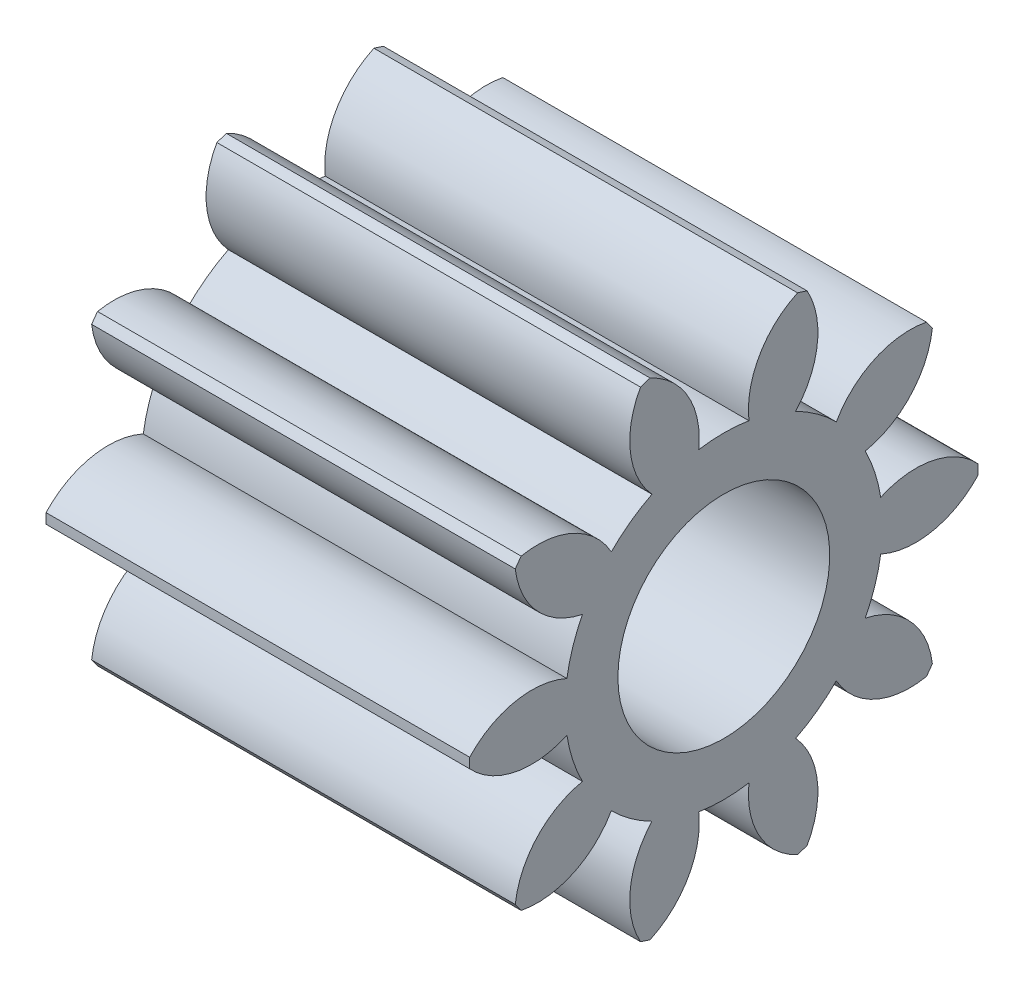
SolidWorks part; units mm, degrees
ref_plane "Plane1" through (0, 0, 0) normal (0, 0, 1) x (1, 0, 0)
ref_plane "Plane2" through (0, 0, 0) normal (0, 1, 0) x (1, 0, 0)
ref_plane "Plane3" through (0, 0, 0) normal (1, 0, 0) x (0, 0, -1)
other "Configuration Table"
sketch "HoldingSke" plane through (0, 0, 0) normal (0, 1, 0) x (1, 0, 0)
  line L0 (0, 0) -> (0.9848, -0.1736)
  line L1 (-15, 0) -> (100, 0) construction
  line L2 (0, 0) -> (-2.1039, 2.3779)
  line L3 (0, 0) -> (-11.863, 4.5341)
  line L4 (0, 0) -> (8.5048, 1.4996)
  line L5 (0, 0) -> (-46.8476, -17.4728)
  line L6 (0, 0) -> (-8.2896, -5.593)
  line L7 (-2.1039, 2.3779) -> (8.6586, 51.2059)
  line L8 (-76.2, 54.61) -> (-75.3, 54.61)
  line L9 (-71.009, 38.7566) -> (-53.1078, 45.2721)
  line L10 (-76.2, 71.12) -> (104.1128, 71.12)
  line L11 (0, 0) -> (-10, 0)
  line L12 (-76.2, 101.6) -> (-76.162, 101.6)
  line L13 (24.9733, 27.94) -> (52.9518, 28.4284)
  line L14 (24.9733, 27.94) -> (24.9743, 27.94)
  line L15 (24.9733, 27.94) -> (100.4006, 29.5858)
  line L16 (-63.627, -1) -> (-12.827, -1)
  circle A0 centre (0, 0) radius 2.5
  circle A1 centre (0, 0) radius 3.749
  circle A2 centre (0, 0) radius 37.5
  circle A3 centre (0, 0) radius 2.5
  dimension "Num_teeth" = 10
  dimension "Pitch_radius" = 180.3128
  dimension "Width" = 10
  dimension "Thickness" = 10
sketch "BasProSke" plane through (0, 0, 0) normal (0, 1, 0) x (1, 0, 0)
  line L0 (-10, 0) -> (60, 0) construction
  line L1 (0, 0) -> (0, 6)
  line L2 (0, 0) -> (10, 0)
  line L3 (10, 0) -> (10, 6)
  line L4 (10, 6) -> (0, 6)
  dimension "Thickness" = 10
  dimension "Diameter" = 12
revolve "Base-Revolve" add sketch "BasProSke" angle 360 about L0
sketch "TooCutSke" plane through (0, 0, 0) normal (1, 0, 0) x (0, 0, -1)
  line L1 (0, 0) -> (0, 107) construction
  line L2 (0, 0) -> (-0.8485, 4.9275) construction
  line L3 (0, 0) -> (-3.0584, 9.4126) construction
  line L4 (-0.8485, 4.9275) -> (-1.5292, 4.7063) construction
  arc A0 (0.5928, 3.7018) -> (-0.5928, 3.7018) centre (0, 0) ccw
  arc A1 (1.7758, 5.7578) -> (-1.7758, 5.7578) centre (0, 0) ccw
  circle A2 centre (0, 0) radius 5 construction
  circle A3 centre (0, 0) radius 4.6985 construction
  arc A4 (-0.5928, 3.7018) -> (-1.7758, 5.7578) centre (-2.5801, 3.9267) ccw
  arc A5 (1.7758, 5.7578) -> (0.5928, 3.7018) centre (2.5801, 3.9267) ccw
extrude "ToothCut" cut sketch "TooCutSke" along normal through all
fillet "Breaks" [suppressed] radius 0.02 tangent propagation no
fillet "RootFillets" [suppressed] radius 0.251
pattern_circular "TeethCuts" count 10 every 36 about axis through (-10, 0, 0) along (1, 0, 0) of "ToothCut", "RootFillets", "Breaks"
sketch "HubNeaOneSke" plane through (0, 0, 0) normal (-1, 0, 0) x (0, 0, 1)
  circle A0 centre (0, 0) radius 3.749
  dimension "Diameter" = 7.498
extrude "HubNearOne" [suppressed] add sketch "HubNeaOneSke" along normal blind 40.0001
sketch "HubNeaBotSke" plane through (0, 0, 0) normal (-1, 0, 0) x (0, 0, 1)
  circle A0 centre (0, 0) radius 3.749
  dimension "Diameter" = 7.498
extrude "HubNearBoth" [suppressed] add sketch "HubNeaBotSke" along normal blind 20
ref_plane "FarPln" through (10, 0, 0) normal (1, 0, 0) x (0, 0, -1)
sketch "HubFarSke" plane through (10, 0, 0) normal (1, 0, 0) x (0, 0, -1)
  circle A0 centre (0, 0) radius 3.749
  dimension "Diameter" = 7.498
extrude "HubFar" [suppressed] add sketch "HubFarSke" along normal blind 20
sketch "BorSke" plane through (0, 0, 0) normal (1, 0, 0) x (0, 0, -1)
  circle A0 centre (0, 0) radius 2.5
  dimension "Diameter" = 5
extrude "Bore" cut sketch "BorSke" along normal mid plane 100.0001
sketch "KeySke" plane through (0, 0, 0) normal (1, 0, 0) x (0, 0, -1)
  line L0 (-1, 0) -> (-1, 3.4)
  line L1 (-1, 3.4) -> (1, 3.4)
  line L2 (1, 3.4) -> (1, 0)
  line L3 (0, 0) -> (0, 34) construction
  line L4 (-1, 0) -> (1, 0)
  dimension "Width" = 2
extrude "Keyway" [suppressed] cut sketch "KeySke" along normal mid plane 100.0001
pattern_circular "Keyway2" [suppressed] count 2 every 90 about axis through (-10, 0, 0) along (1, 0, 0) reverse direction yes
equation "' \"Module@HoldingSke\" = 6.35"
equation "' \"Num_teeth@HoldingSke\" = 12"
equation "' \"Ap@HoldingSke\" =  20"
equation "' \"Ap@HoldingSke\" = 20"
equation "' \"Width@HoldingSke\" = 0.5 * 25.4"
equation "' \"Hub_dia@HoldingSke\"= 1 * 25.4"
equation "' \"Hub_dia@HoldingSke\" = 1 * 25.4"
equation "' \"Overall_len@HoldingSke\" = 1.0 * 25.4"
equation "' \"Bore@HoldingSke\" = 0.75 * 25.4"
equation "' \"T_dim@HoldingSke\" = 0.1 * 25.4"
equation "' \"Width@KeySke\" = 0.25 * 25.4"
equation "' \"Show_teeth@HoldingSke\" = 13"
equation "' \"Backlash@HoldingSke\" = 0.009 * 25.4"
equation "' \"Addendum_fac@HoldingSke\" = 1.0"
equation "' \"Dedendum_fac@HoldingSke\" = 1.25"
equation "' \"Dedendum_add@HoldingSke\" = 0.00005 * 25.4"
equation "' \"Clearance_fac@HoldingSke\" = 0.25"
equation "\"Pitch@HoldingSke\" = 1 / \"Module@HoldingSke\""
equation "\"Overcut_dia@TooCutSke\" = (\"Num_teeth@HoldingSke\" + 2 * \"Addendum_fac@HoldingSke\") / \"Pitch@HoldingSke\" + 0.002 * 25.4"
equation "\"Pitch_dia@TooCutSke\" = \"Num_teeth@HoldingSke\" / \"Pitch@HoldingSke\""
equation "\"Base_dia@TooCutSke\" = \"Num_teeth@HoldingSke\" / \"Pitch@HoldingSke\" * cos((\"Ap@HoldingSke\"  * 3.14159265 / 180))"
equation "\"Root_dia@TooCutSke\" = (\"Num_teeth@HoldingSke\" + 2) / \"Pitch@HoldingSke\" - 2 * (\"Addendum_fac@HoldingSke\" + \"Dedendum_fac@HoldingSke\") / \"Pitch@HoldingSke\" - \"Dedendum_add@HoldingSke\" * 2"
equation "\"Half_ang@TooCutSke\" = 180 / \"Num_teeth@HoldingSke\""
equation "\"Half_CT@TooCutSke\" = \"Num_teeth@HoldingSke\" / \"Pitch@HoldingSke\" * sin((3.14159265 / 2 / \"Num_teeth@HoldingSke\")) / 2 - 7 * \"Backlash@HoldingSke\" / 4"
equation "\"Flank_rad@TooCutSke\" = \"Num_teeth@HoldingSke\" / \"Pitch@HoldingSke\" / 5"
equation "\"Radius@RootFillets\" = \"Clearance_fac@HoldingSke\" / \"Pitch@HoldingSke\" + \"Dedendum_add@HoldingSke\""
equation "\"Break_rad@Breaks\" = 0.02 / \"Pitch@HoldingSke\""
equation "\"Thickness@HoldingSke\" = \"Width@HoldingSke\""
equation "\"OAL@HoldingSke\" = \"Thickness@HoldingSke\""
equation "\"MHD@HoldingSke\" = (\"Num_teeth@HoldingSke\" + 2) / \"Pitch@HoldingSke\" - 2 * (\"Addendum_fac@HoldingSke\" + \"Dedendum_fac@HoldingSke\")  / \"Pitch@HoldingSke\" - \"Dedendum_add@HoldingSke\" * 2"
equation "\"MBD@HoldingSke\" = (\"Num_teeth@HoldingSke\" + 2) / \"Pitch@HoldingSke\" - 2 * (\"Addendum_fac@HoldingSke\" + \"Dedendum_fac@HoldingSke\")  / \"Pitch@HoldingSke\" - \"Dedendum_add@HoldingSke\" * 2 - 0.002 * 25.4"
equation "\"MHD@HoldingSke\" = ((sgn( \"MHD@HoldingSke\" - \"Hub_dia@HoldingSke\" )-1)*( \"MHD@HoldingSke\" - \"Hub_dia@HoldingSke\" ))/-2+ \"Hub_dia@HoldingSke\""
equation "\"MBD@HoldingSke\" = ((sgn( \"MBD@HoldingSke\" - \"Bore@HoldingSke\" )-1)*( \"MBD@HoldingSke\" - \"Bore@HoldingSke\" ))/-2+ \"Bore@HoldingSke\""
equation "\"OAL@HoldingSke\" = ((sgn( \"OAL@HoldingSke\" - \"Overall_len@HoldingSke\" )+1)*( \"OAL@HoldingSke\" - \"Overall_len@HoldingSke\" ))/2 + \"Overall_len@HoldingSke\" + 0.000002 * 25.4"
equation "\"Num_teeth@TeethCuts\" = int( \"Show_teeth@HoldingSke\" ) + 1"
equation "\"Num_teeth@TeethCuts\" = ((sgn( \"Num_teeth@TeethCuts\" - \"Num_teeth@HoldingSke\" )-1)*( \"Num_teeth@TeethCuts\" - \"Num_teeth@HoldingSke\" ))/-2+ \"Num_teeth@HoldingSke\""
equation "\"Num_teeth@TeethCuts\" = ((sgn( \"Num_teeth@TeethCuts\" - 2.0)+1)*( \"Num_teeth@TeethCuts\" - 2.0))/2 +2.0"
equation "\"Angle@TeethCuts\" = 360.0 / \"Num_teeth@HoldingSke\""
equation "\"Diameter@BasProSke\" = (\"Num_teeth@HoldingSke\" + 2 * \"Addendum_fac@HoldingSke\") / \"Pitch@HoldingSke\""
equation "\"Thickness@BasProSke\"  = \"Thickness@HoldingSke\""
equation "' \"Fillet_rad@BasProSke\" =  \"Thickness@HoldingSke\" * 0.05"
equation "' \"Fillet_rad@BasProSke\" = \"Thickness@HoldingSke\" * 0.05"
equation "\"MHD@HoldingSke\" = ((sgn( \"MHD@HoldingSke\" - \"Root_dia@TooCutSke\" )-1)*( \"MHD@HoldingSke\" - \"Root_dia@TooCutSke\" ))/-2+ \"Root_dia@TooCutSke\""
equation "\"Diameter@HubNeaOneSke\" = \"MHD@HoldingSke\""
equation "\"Length@HubNearOne\" = \"OAL@HoldingSke\" - \"Thickness@BasProSke\""
equation "\"Diameter@HubNeaBotSke\" = \"MHD@HoldingSke\""
equation "\"Length@HubNearBoth\" = ( \"OAL@HoldingSke\" - \"Thickness@BasProSke\" ) / 2.0"
equation "\"Thickness@FarPln\" = \"Thickness@BasProSke\""
equation "\"Diameter@HubFarSke\" = \"MHD@HoldingSke\""
equation "\"Length@HubFar\" = ( \"OAL@HoldingSke\" - \"Thickness@BasProSke\" ) / 2.0"
equation "\"Diameter@BorSke\" = \"MBD@HoldingSke\""
equation "\"D1@Bore\" = \"OAL@HoldingSke\" * 2.0"
equation "\"D1@Keyway\" = \"OAL@HoldingSke\" * 2.0"
equation "\"Offset@KeySke\" = \"T_dim@HoldingSke\" + \"MBD@HoldingSke\" / 2.0"
